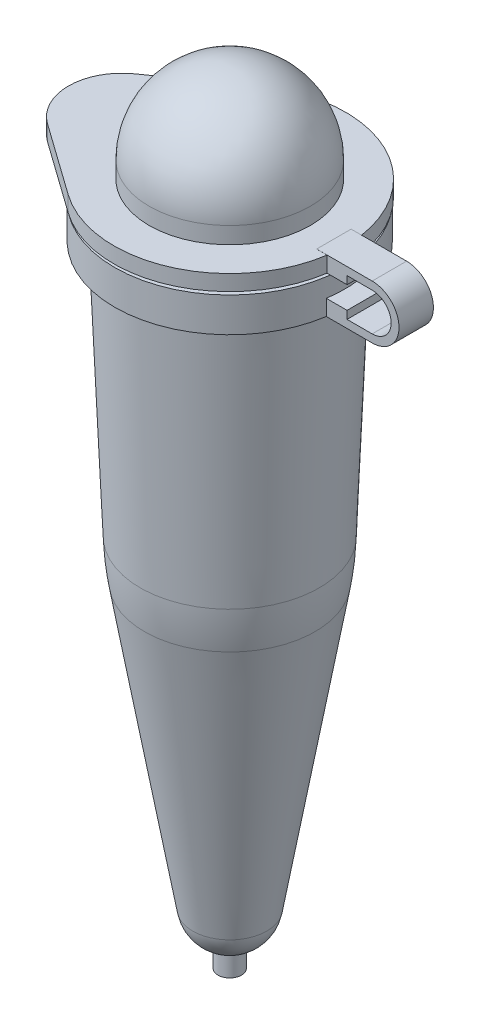
SolidWorks part; units mm, degrees
ref_plane "Front Plane" through (0, 0, 0) normal (0, 0, 1) x (1, 0, 0)
ref_plane "Top Plane" through (0, 0, 0) normal (0, 1, 0) x (1, 0, 0)
ref_plane "Right Plane" through (0, 0, 0) normal (1, 0, 0) x (0, 0, -1)
sketch "Sketch1" plane through (0, 0, 0) normal (0, 1, 0) x (1, 0, 0)
  circle A0 centre (0, 0) radius 3.7338
  circle A1 centre (0, 0) radius 2.6797
  dimension "D1" = 7.4676
  dimension "D2" = 5.3594
extrude "Boss-Extrude1" add sketch "Sketch1" against normal blind 1.1176
sketch "Sketch2" plane through (0, 0, 0) normal (0, 0, 1) x (1, 0, 0)
  line L0 (0, -1.1176) -> (0, -20.9296)
  line L1 (-3.2385, -1.1176) -> (-2.9065, -9.4171)
  line L2 (-3.7338, -1.1176) -> (3.7338, -1.1176) construction
  line L3 (-2.7708, -10.7148) -> (-1.2065, -19.911)
  line L4 (-3.2385, -1.1176) -> (0, -1.1176)
  arc A0 (-1.2065, -19.911) -> (0, -20.9296) centre (0, -19.7058) ccw
  arc A1 (-2.9065, -9.4171) -> (-2.7708, -10.7148) centre (7.2454, -9.0111) ccw
  arc A4 (0, -20.909) -> (1.2062, -19.8923) centre (0, -19.6852) ccw construction
  point P7 (-2.9591, -8.1026)
  point P10 (-2.8479, -10.2616)
  dimension "D5" = 10.16
  dimension "D1" = 3.2385
  dimension "D2" = 6.985
  dimension "D3" = 2.9591
  dimension "D4" = 9.144
  dimension "D8" = 19.812
revolve "Revolve1" add sketch "Sketch2" angle 360 about L0
shell "Shell1" thickness 0.5715 removed face at (-3.2385, -1.1176, 0)
combine bodies "Combine1" operation type add bodies to combine 101 102
sketch "Sketch3" plane through (0, 0, 0) normal (0, 0, 1) x (1, 0, 0)
  line L0 (3.7338, -1.1176) -> (4.3653, -1.1176)
  line L1 (4.3653, -0.8625) -> (4.3653, -0.6074)
  line L2 (4.3653, -0.6074) -> (3.3793, -0.6074)
  line L3 (3.3793, -0.6074) -> (3.3793, -1.1176)
  line L4 (-3.7338, -1.1176) -> (3.7338, -1.1176) construction
  line L5 (3.3793, -1.1176) -> (3.7338, -1.1176)
  line L6 (4.3653, -1.1176) -> (5.18, -1.1176)
  line L8 (5.18, -0.8625) -> (4.3653, -0.8625)
  line L9 (3.3793, 0.1127) -> (4.3653, 0.1127)
  line L10 (4.3653, 0.1127) -> (4.3653, 0.3677)
  line L11 (4.3653, 0.6228) -> (3.3793, 0.6228)
  line L12 (3.3793, 0.6228) -> (3.3793, 0.1127)
  line L13 (4.3653, 0.6228) -> (5.18, 0.6228)
  line L15 (5.18, 0.3677) -> (4.3653, 0.3677)
  arc A0 (5.18, 0.6228) -> (5.18, -1.1176) centre (5.18, -0.2474) cw
  arc A1 (5.18, 0.3677) -> (5.18, -0.8625) centre (5.18, -0.2474) cw
extrude "Boss-Extrude2" add sketch "Sketch3" along normal mid plane 1.1176
sketch "Sketch4" plane through (0, 0.1127, 0) normal (0, -1, 0) x (1, 0, 0)
  circle A0 centre (0, 0) radius 2.615
  circle A1 centre (0, 0) radius 2.107
  dimension "D1" = 0.508
extrude "Boss-Extrude3" add sketch "Sketch4" along normal blind 1.1176 separate body
sketch "Sketch5" plane through (0, 0, 0) normal (0, 0, 1) x (1, 0, 0)
  line L0 (-2.615, 0.1127) -> (-2.615, 1.1608)
  line L1 (-2.107, 0.1127) -> (-2.107, 1.1608)
  line L4 (0, 3.7758) -> (0, 3.2678)
  line L5 (-2.615, 0.1127) -> (-2.615, 0.0475)
  line L6 (-2.615, 0.1127) -> (-2.615, -1.0049) construction
  line L7 (-2.615, 0.0475) -> (-2.107, 0.0475)
  line L8 (-2.107, 0.0475) -> (-2.107, 0.1127)
  arc A0 (0, 3.7758) -> (-2.615, 1.1608) centre (0, 1.1608) ccw
  arc A1 (0, 3.2678) -> (-2.107, 1.1608) centre (0, 1.1608) ccw
revolve "Revolve2" add sketch "Sketch5" angle 360 about L4
sketch "Sketch6" plane through (0, 0.1127, 0) normal (0, -1, 0) x (1, 0, 0)
  line L0 (-2.1799, -3.0626) -> (-4.5074, -1.4059)
  line L1 (0, 0) -> (1.7312, 0) construction
  line L2 (-2.1799, 3.0626) -> (-4.5074, 1.4059)
  arc A0 (-2.1799, -3.0626) -> (-2.1799, 3.0626) centre (0, 0) ccw
  arc A1 (-4.5074, 1.4059) -> (-4.5074, -1.4059) centre (-3.5067, 0) ccw
  point P5 (3.7592, 0)
  point P6 (-5.2324, 0)
  dimension "D1" = 7.5184
  dimension "D2" = 8.9916
extrude "Boss-Extrude4" add sketch "Sketch6" against normal blind 0.508
sketch "Sketch7" plane through (0, 0, 0) normal (0, 0, 1) x (1, 0, 0)
  line L1 (0, -20.6309) -> (-0.381, -20.6309)
  line L2 (0, -20.6309) -> (0, -21.5646)
  line L3 (0, -21.5646) -> (-0.381, -21.5646)
  line L4 (-0.381, -20.6309) -> (-0.381, -21.5646)
  arc A0 (-1.2065, -19.911) -> (1.2065, -19.911) centre (0, -19.7058) ccw construction
  point P4 (0, -20.9296)
  dimension "D1" = 0.635
  dimension "D2" = 0.381
revolve "Revolve3" add sketch "Sketch7" angle 360 about L2
